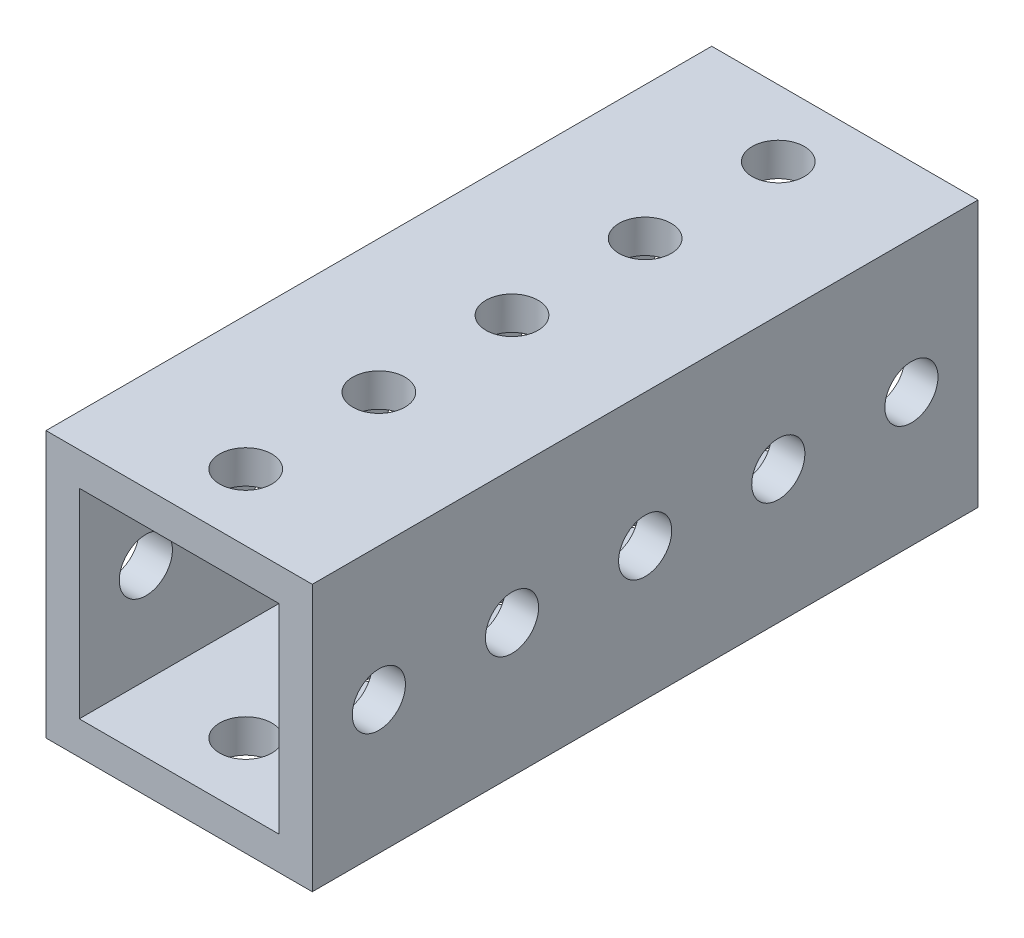
SolidWorks part; units mm, degrees
material "6061-T6 (SS)"
ref_plane "Front Plane" through (0, 0, 0) normal (0, 0, 1) x (1, 0, 0)
ref_plane "Top Plane" through (0, 0, 0) normal (0, 1, 0) x (1, 0, 0)
ref_plane "Right Plane" through (0, 0, 0) normal (1, 0, 0) x (0, 0, -1)
sketch "Sketch1" plane through (0, 0, 0) normal (0, 0, 1) x (1, 0, 0)
  line L1 (0, 0) -> (25.4, 0)
  line L2 (0, 0) -> (0, 25.4)
  line L3 (0, 25.4) -> (25.4, 25.4)
  line L4 (25.4, 0) -> (25.4, 25.4)
  dimension "D1" = 25.4
  dimension "D2" = 25.4
extrude "Boss-Extrude1" add sketch "Sketch1" along normal blind 63.5
shell "Shell1" thickness 3.175 removed face at (12.7, 12.7, 0) removed face at (12.7, 12.7, 63.5)
sketch "Sketch2" plane through (0, 25.4, 0) normal (0, 1, 0) x (1, 0, 0)
  line L0 (25.4, 0) -> (0, 0) construction
  line L1 (0, -63.5) -> (0, 0) construction
  circle A0 centre (12.7, -6.35) radius 2.4892
  circle A1 centre (12.7, -19.05) radius 2.4892
  circle A2 centre (12.7, -31.75) radius 2.4892
  circle A3 centre (12.7, -44.45) radius 2.4892
  circle A4 centre (12.7, -57.15) radius 2.4892
  dimension "D1" = 4.9784
  dimension "D3" = 12.7
  dimension "D5" = 12.7
  dimension "D2" = 6.35
  dimension "D4" = 5
extrude "Cut-Extrude1" cut sketch "Sketch2" against normal blind 63.5
sketch "Sketch3" plane through (25.4, 0, 0) normal (1, 0, 0) x (0, 0, -1)
  line L0 (-63.5, 25.4) -> (0, 25.4) construction
  line L1 (-63.5, 0) -> (-63.5, 25.4) construction
  circle A0 centre (-57.15, 12.7) radius 2.5349
  circle A1 centre (-44.45, 12.7) radius 2.5349
  circle A2 centre (-31.75, 12.7) radius 2.5349
  circle A3 centre (-19.05, 12.7) radius 2.5349
  circle A4 centre (-6.35, 12.7) radius 2.5349
  dimension "D1" = 5.0698
  dimension "D5" = 12.7
  dimension "D2" = 12.7
  dimension "D3" = 6.35
  dimension "D4" = 5
extrude "Cut-Extrude2" cut sketch "Sketch3" against normal blind 63.5
